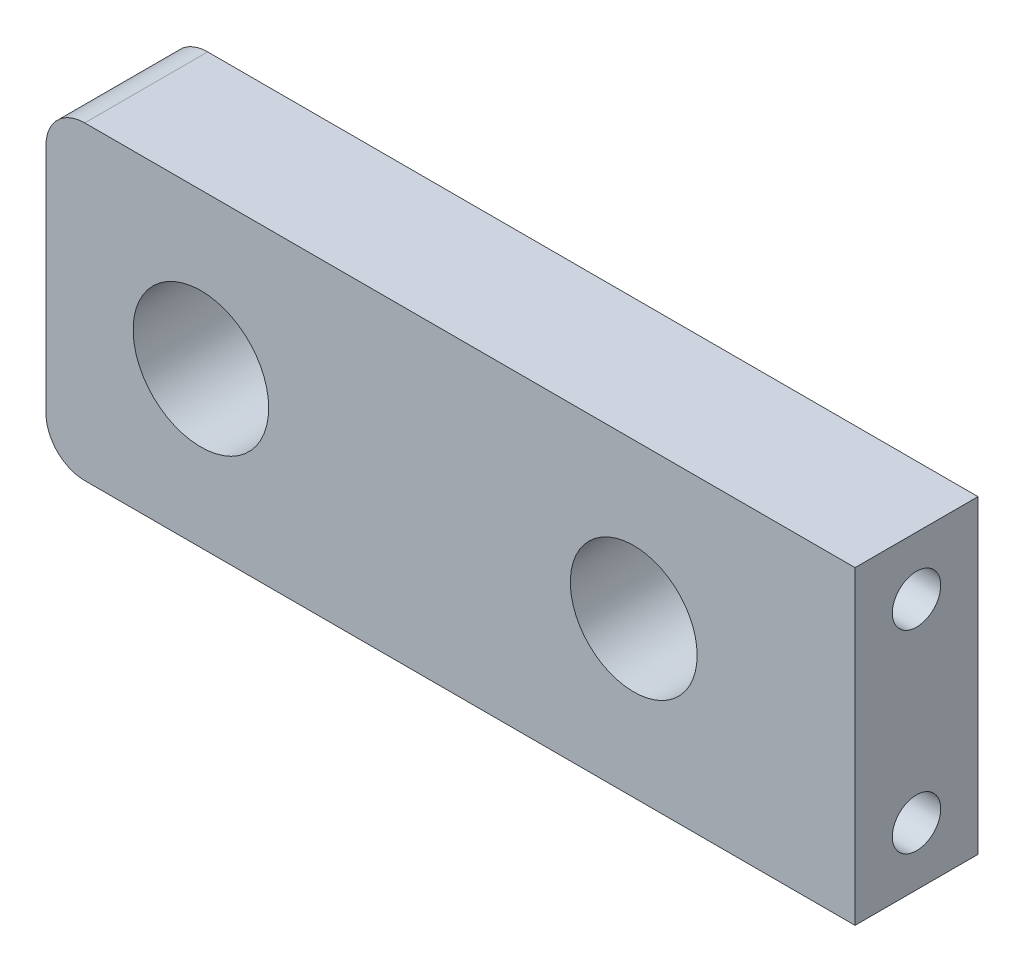
SolidWorks part; units mm, degrees
ref_plane "Front Plane" through (0, 0, 0) normal (0, 0, 1) x (1, 0, 0)
ref_plane "Top Plane" through (0, 0, 0) normal (0, 1, 0) x (1, 0, 0)
ref_plane "Right Plane" through (0, 0, 0) normal (1, 0, 0) x (0, 0, -1)
sketch "Sketch1" plane through (0, 0, 0) normal (0, 0, 1) x (1, 0, 0)
  line L0 (41.782, 8) -> (0, 8) construction
  line L1 (0, 0) -> (41.782, 0)
  line L2 (0, 0) -> (0, 16)
  line L3 (0, 16) -> (41.782, 16)
  line L4 (41.782, 0) -> (41.782, 16)
  circle A0 centre (8, 8) radius 3.5
  circle A1 centre (30.352, 8) radius 3.275
  point P11 (0, 0)
  point P12 (0, 0)
  point P13 (0, 0)
  dimension "D5" = 7
  dimension "D6" = 6.55
  dimension "D1" = 11.43
  dimension "D2" = 16
  dimension "D3" = 22.352
  dimension "D4" = 8
extrude "Boss-Extrude1" add sketch "Sketch1" along normal blind 6.35 contours L3 L4 L1 L2
extrude "Cut-Extrude1" cut sketch "Sketch1<6>" along normal blind 6.35 contours A0 L0 | L0 A0 | A1 region at (8, 6.5146, 0) region at (8, 9.4854, 0)
sketch "Sketch1<6>" plane through (0, 0, 0) normal (0, 0, 1) x (1, 0, 0) same geometry as "Sketch1"
fillet "Fillet1" radius 2 2 edges at (0, 16, 3.175) (0, 0, 3.175)
sketch "Sketch2" plane through (41.782, 0, 0) normal (1, 0, 0) x (0, 0, -1)
  line L0 (-6.35, 16) -> (0, 16) construction
  line L1 (-6.35, 0) -> (0, 0) construction
  line L4 (-6.35, 0) -> (-6.35, 16) construction
  circle A0 centre (-3.175, 13) radius 1.25
  circle A1 centre (-3.175, 3) radius 1.25
  point P10 (-6.35, 6.6525)
  point P11 (-2.0568, -6.4668)
  dimension "D1" = 2.5
  dimension "D2" = 2.5
  dimension "D3" = 3
  dimension "D4" = 3
  dimension "D5" = 3.175
  dimension "D6" = 3.175
extrude "Cut-Extrude2" cut sketch "Sketch2" against normal blind 4
